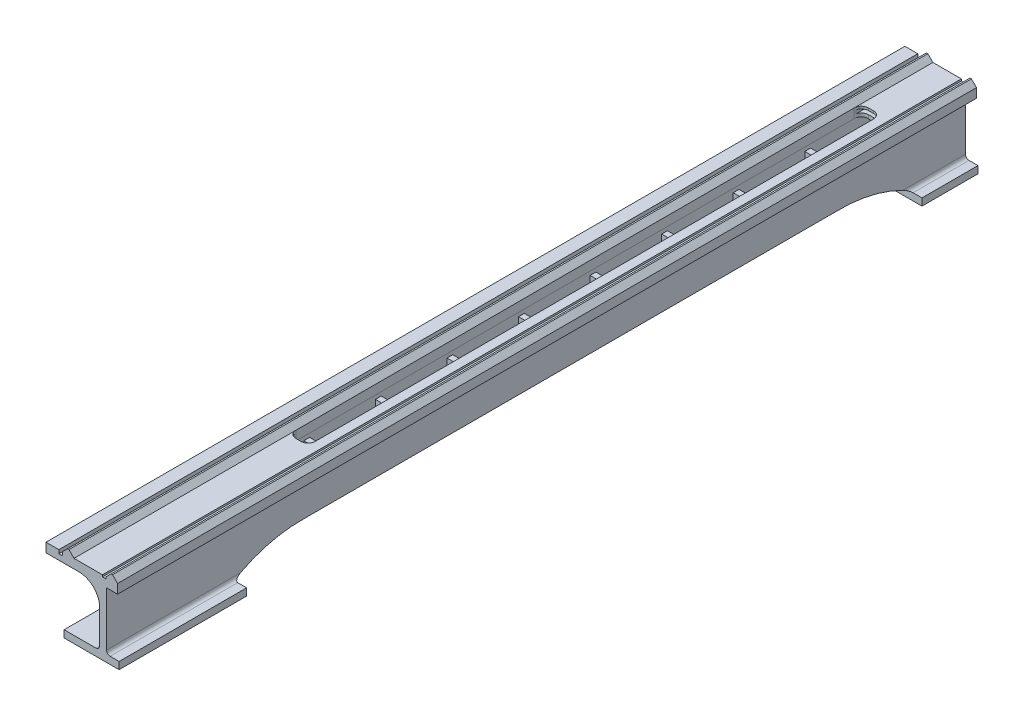
SolidWorks part; units mm, degrees
ref_plane "Front Plane" through (0, 0, 0) normal (0, 0, 1) x (1, 0, 0)
ref_plane "Top Plane" through (0, 0, 0) normal (0, 1, 0) x (1, 0, 0)
ref_plane "Right Plane" through (0, 0, 0) normal (1, 0, 0) x (0, 0, -1)
sketch "Sketch1" plane through (0, 0, 0) normal (0, 0, 1) x (1, 0, 0)
  line L0 (-33.3128, 35.4652) -> (-40.3839, 42.5363)
  line L2 (-133.3128, 35.4652) -> (-133.3128, 22.5363)
  line L4 (-33.3128, 35.4652) -> (-33.3128, 22.5363)
  line L5 (-40.3839, 42.5363) -> (-42.3839, 42.5363)
  line L6 (-42.3839, 42.5363) -> (-49.455, 35.4652)
  line L7 (-49.455, 35.4652) -> (-49.455, 32.891)
  line L8 (-49.455, 32.891) -> (-54.455, 32.891)
  line L9 (-54.455, 32.891) -> (-54.455, 35.4652)
  line L10 (-54.455, 35.4652) -> (-94.1707, 35.4652)
  line L14 (-94.1707, 35.4652) -> (-101.2418, 42.5363)
  line L15 (-101.2418, 42.5363) -> (-103.2418, 42.5363)
  line L16 (-103.2418, 42.5363) -> (-110.3128, 35.4652)
  line L17 (-110.3128, 35.4652) -> (-110.3128, 30.4818)
  line L18 (-110.3128, 30.4818) -> (-115.3128, 30.4818)
  line L19 (-115.3128, 30.4818) -> (-115.3128, 35.4652)
  line L20 (-115.3128, 35.4652) -> (-133.3128, 35.4652)
  line L21 (-133.3128, 22.5363) -> (-87.3496, 22.5363)
  line L22 (-33.3128, 22.5363) -> (-48.7011, 22.5363)
  line L23 (-48.7011, 22.5363) -> (-48.7011, -52.7938)
  line L24 (-43.7011, -57.7938) -> (-31.1954, -57.7938)
  line L25 (-31.1954, -57.7938) -> (-31.1954, -67.7938)
  line L26 (-31.1954, -67.7938) -> (-108.01, -67.7938)
  line L27 (-108.01, -67.7938) -> (-108.01, -57.7938)
  line L28 (-108.01, -57.7938) -> (-63.7011, -57.7938)
  line L29 (-58.7011, -52.7938) -> (-58.7011, -0.8365)
  arc A0 (-87.3496, 22.5363) -> (-58.7011, -0.8365) centre (-87.3496, -6.7076) cw
  arc A1 (-48.7011, -52.7938) -> (-43.7011, -57.7938) centre (-43.7011, -52.7938) ccw
  arc A2 (-63.7011, -57.7938) -> (-58.7011, -52.7938) centre (-63.7011, -52.7938) ccw
  point P30 (-48.7011, -57.7938)
  dimension "D17" = 5
  dimension "D1" = 100
  dimension "D2" = 10
  dimension "D3" = 2
  dimension "D4" = 5
  dimension "D5" = 18
  dimension "D6" = 5
  dimension "D7" = 20
  dimension "D8" = 135
  dimension "D9" = 10
  dimension "D10" = 10
  dimension "D11" = 2
  dimension "D12" = 10
  dimension "D13" = 10
  dimension "D14" = 58.8579
  dimension "D15" = 10
  dimension "D16" = 20
extrude "Boss-Extrude1" add sketch "Sketch1" along normal blind 1200
sketch "Sketch2" plane through (0, 20.7647, 0) normal (0, 1, 0) x (1, 0, 0)
  line L0 (-94.1707, -1200) -> (-94.1707, 0) construction
  line L1 (-84.1707, -100) -> (-77.1707, -100)
  line L2 (-94.1707, -110) -> (-94.1707, -890)
  line L3 (-84.1707, -900) -> (-77.1707, -900)
  line L4 (-67.1707, -110) -> (-67.1707, -890)
  line L5 (-67.1707, -1200) -> (-67.1707, 0) construction
  line L6 (-54.455, 0) -> (-94.1707, 0) construction
  arc A0 (-94.1707, -890) -> (-84.1707, -900) centre (-84.1707, -890) ccw
  arc A1 (-77.1707, -900) -> (-67.1707, -890) centre (-77.1707, -890) ccw
  arc A2 (-77.1707, -100) -> (-67.1707, -110) centre (-77.1707, -110) cw
  arc A3 (-84.1707, -100) -> (-94.1707, -110) centre (-84.1707, -110) ccw
  point P12 (-67.1707, -900)
  point P15 (-67.1707, -100)
  point P18 (-94.1707, -100)
  dimension "D2" = 10
  dimension "D1" = 800
  dimension "D3" = 100
extrude "Cut-Extrude1" cut sketch "Sketch2" along normal blind 800
sketch "Sketch3" plane through (0, 0, 1200) normal (0, 0, 1) x (1, 0, 0)
  line L1 (-61.1129, 27.3205) -> (-93.9675, 27.3205)
  line L2 (-61.1129, 27.3205) -> (-61.1129, 32.1773)
  line L3 (-61.1129, 32.1773) -> (-93.9675, 32.1773)
  line L4 (-93.9675, 27.3205) -> (-93.9675, 32.1773)
extrude "Cut-Extrude2" cut sketch "Sketch3" against normal blind 900 from offset 300 offset against normal yes
sketch "Sketch5" plane through (0, 0, 0) normal (0, 0, -1) x (-1, 0, 0)
  line L1 (101.3003, -59.4347) -> (94.9198, -59.4347)
  line L2 (101.3003, -59.4347) -> (101.3003, 27.7967)
  line L3 (101.3003, 27.7967) -> (94.9198, 27.7967)
  line L4 (94.9198, -59.4347) -> (94.9198, 27.7967)
extrude "Boss-Extrude2" add sketch "Sketch5" against normal blind 1100
sketch "Sketch6" plane through (-101.3003, 0, 0) normal (-1, 0, 0) x (0, 0, 1)
  line L1 (70.1556, 16.5847) -> (78.2516, 16.5847)
  line L2 (70.1556, 16.5847) -> (70.1556, -47.4448)
  line L3 (70.1556, -47.4448) -> (78.2516, -47.4448)
  line L4 (78.2516, 16.5847) -> (78.2516, -47.4448)
extrude "Boss-Extrude3" add sketch "Sketch6" against normal blind 50
pattern_linear "LPattern1" count 10 spacing 100 along (0, 0, 1) of "Boss-Extrude3"
sketch "Sketch4" plane through (-33.3128, 0, 0) normal (1, 0, 0) x (0, 0, -1)
  line L0 (-1021.7946, -57.7938) -> (-1021.7946, -67.7938)
  line L1 (-1200, -57.7938) -> (0, -57.7938) construction
  line L2 (-1200, -67.7938) -> (0, -67.7938) construction
  line L3 (-1021.7946, -67.7938) -> (-1021.7946, -177.9566)
  line L4 (-1021.7946, -177.9566) -> (-78.2516, -177.9566)
  line L5 (-78.2516, -177.9566) -> (-78.2516, -57.7938)
  line L6 (-924.3184, -31.7513) -> (-180.0688, -31.7513)
  arc A1 (-924.3184, -31.7513) -> (-1021.7946, -57.7938) centre (-927.5791, -214.9931) ccw
  arc A2 (-180.0688, -31.7513) -> (-78.2516, -57.7938) centre (-175.6333, -226.4665) cw
extrude "Cut-Extrude3" cut sketch "Sketch4" against normal blind 100 and the other way blind 10
